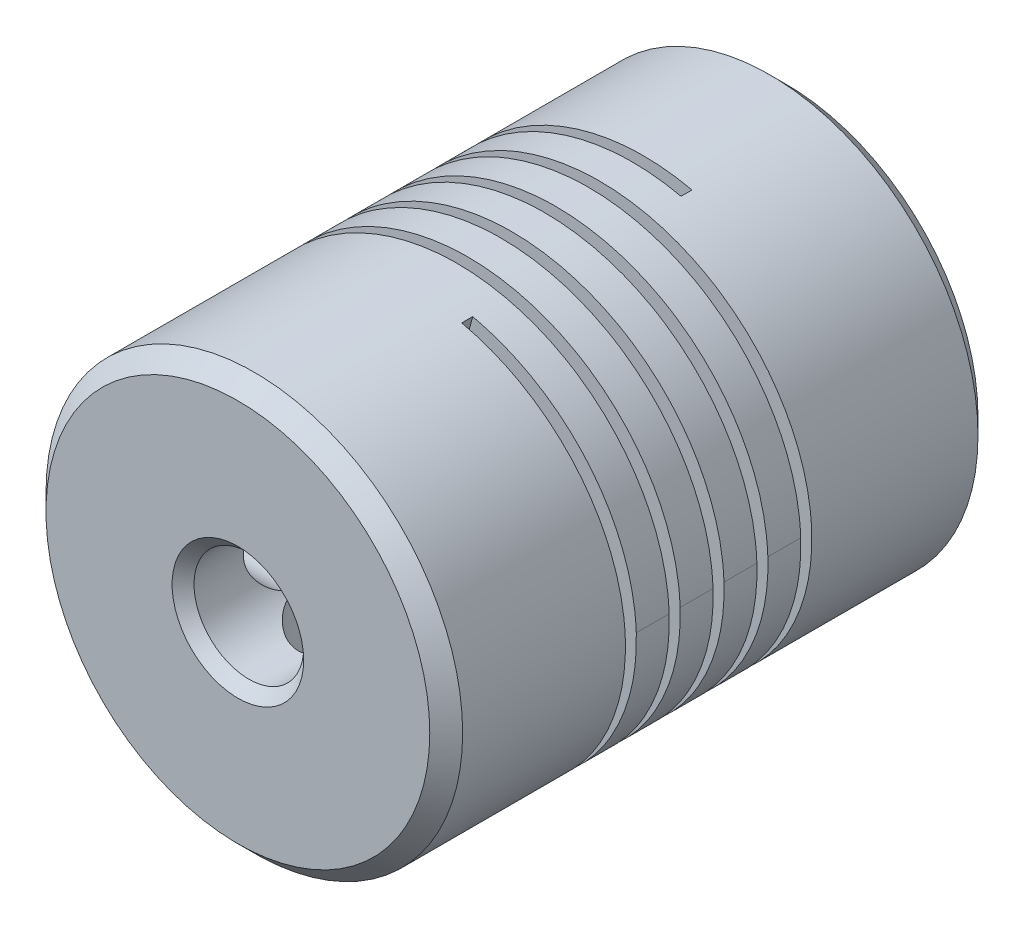
SolidWorks part; units mm, degrees
material "6063-T5"
ref_plane "Спереди" through (0, 0, 0) normal (0, 0, 1) x (1, 0, 0)
ref_plane "Сверху" through (0, 0, 0) normal (0, 1, 0) x (1, 0, 0)
ref_plane "Справа" through (0, 0, 0) normal (1, 0, 0) x (0, 0, -1)
sketch "Эскиз1" plane through (0, 0, 0) normal (0, 0, 1) x (1, 0, 0)
  circle A0 centre (0, 0) radius 9.5
  dimension "D1" = 19
extrude "Body" add sketch "Эскиз1" along normal blind 25
sketch "Эскиз2" plane through (0, 0, 25) normal (0, 0, 1) x (1, 0, 0)
  circle A0 centre (0, 0) radius 2.5
  dimension "D1" = 5
extrude "RodHole" cut sketch "Эскиз2" against normal blind 42
chamfer "OuterChamfer" distance 0.75 angle 45 2 edges at (9.5, 0, 25) (9.5, 0, 0)
chamfer "InnerChamfer" distance 0.5 angle 45 2 edges at (2.5, 0, 25) (2.5, 0, 0)
sketch "Эскиз3" plane through (0, 0, 0) normal (1, 0, 0) x (0, 0, -1)
  circle A0 centre (-4.5, 0) radius 1.75
  circle A1 centre (-20.5, 0) radius 1.75
  dimension "D1" = 3.5
  dimension "D2" = 3.5
  dimension "D3" = 4.5
  dimension "D4" = 20.5
extrude "SetScrewHoles1" cut sketch "Эскиз3" against normal blind 12
cosmetic thread "Условное изображение резьбы1" parameters "D2"=4
cosmetic thread "Условное изображение резьбы2" parameters "D2"=4
sketch "Эскиз4" plane through (0, 0, 0) normal (0, 1, 0) x (1, 0, 0)
  circle A0 centre (0, -4.5) radius 1.75
  circle A1 centre (0, -20.5) radius 1.75
  dimension "D1" = 3.5
  dimension "D2" = 3.5
  dimension "D3" = 4.5
  dimension "D4" = 20.5
extrude "SetScrewHoles2" cut sketch "Эскиз4" against normal blind 12
cosmetic thread "Условное изображение резьбы3" parameters "D2"=4
cosmetic thread "Условное изображение резьбы4" parameters "D2"=4
ref_plane "ReferencePlane1" through (0, 0, 17) normal (0, 0, 1) x (1, 0, 0)
sketch "Эскиз6" plane through (0, 0, 17) normal (0, 0, 1) x (1, 0, 0)
  circle A0 centre (0, 0) radius 9.5
curve "SlotTrajectory" pitch 2 height 10 radius 9.5 centre (0, 0, 17) axis (0, 0, -1) start towards (0.2588, 0.9659, 0)
ref_plane "ReferencePlane2" through (0, 0, 0) normal (0.9659, -0.2588, 0) x (0, 0, -1)
sketch "Эскиз7" plane through (0, 0, 0) normal (0.9659, -0.2588, 0) x (0, 0, -1)
  line L0 (-0.75, 9.5) -> (-24.25, 9.5) construction
  line L1 (-6.75, 10.0798) -> (-7.25, 10.0798)
  line L2 (-6.75, 10.0798) -> (-6.75, 1.4319)
  line L3 (-6.75, 1.4319) -> (-7.25, 1.4319)
  line L4 (-7.25, 10.0798) -> (-7.25, 1.4319)
  spline S0 degree 3 poles (-17, 9.5) (-16.9586, 9.5) (-16.8749, 9.0054) (-16.75, 6.8924) (-16.625, 3.7301) (-16.5, 0) (-16.375, -3.7301) (-16.25, -6.8924) (-16.125, -9.0054) (-16, -9.7473) (-15.875, -9.0054) (-15.75, -6.8924) (-15.625, -3.7301) (-15.5, 0) (-15.375, 3.7301) (-15.25, 6.8924) (-15.125, 9.0054) (-15, 9.7473) (-14.875, 9.0054) (-14.75, 6.8924) (-14.625, 3.7301) (-14.5, 0) (-14.375, -3.7301) (-14.25, -6.8924) (-14.125, -9.0054) (-14, -9.7473) (-13.875, -9.0054) (-13.75, -6.8924) (-13.625, -3.7301) (-13.5, 0) (-13.375, 3.7301) (-13.25, 6.8924) (-13.125, 9.0054) (-13, 9.7473) (-12.875, 9.0054) (-12.75, 6.8924) (-12.625, 3.7301) (-12.5, 0) (-12.375, -3.7301) (-12.25, -6.8924) (-12.125, -9.0054) (-12, -9.7473) (-11.875, -9.0054) (-11.75, -6.8924) (-11.625, -3.7301) (-11.5, 0) (-11.375, 3.7301) (-11.25, 6.8924) (-11.125, 9.0054) (-11, 9.7473) (-10.875, 9.0054) (-10.75, 6.8924) (-10.625, 3.7301) (-10.5, 0) (-10.375, -3.7301) (-10.25, -6.8924) (-10.125, -9.0054) (-10, -9.7473) (-9.875, -9.0054) (-9.75, -6.8924) (-9.625, -3.7301) (-9.5, 0) (-9.375, 3.7301) (-9.25, 6.8924) (-9.125, 9.0054) (-9, 9.7473) (-8.875, 9.0054) (-8.75, 6.8924) (-8.625, 3.7301) (-8.5, 0) (-8.375, -3.7301) (-8.25, -6.8924) (-8.125, -9.0054) (-8, -9.7473) (-7.875, -9.0054) (-7.75, -6.8924) (-7.625, -3.7301) (-7.5, 0) (-7.375, 3.7301) (-7.25, 6.8924) (-7.1251, 9.0054) (-7.0414, 9.5) (-7, 9.5) knots 0 0 0 0 0.0125 0.025 0.0375 0.05 0.0625 0.075 0.0875 0.1 0.1125 0.125 0.1375 0.15 0.1625 0.175 0.1875 0.2 0.2125 0.225 0.2375 0.25 0.2625 0.275 0.2875 0.3 0.3125 0.325 0.3375 0.35 0.3625 0.375 0.3875 0.4 0.4125 0.425 0.4375 0.45 0.4625 0.475 0.4875 0.5 0.5125 0.525 0.5375 0.55 0.5625 0.575 0.5875 0.6 0.6125 0.625 0.6375 0.65 0.6625 0.675 0.6875 0.7 0.7125 0.725 0.7375 0.75 0.7625 0.775 0.7875 0.8 0.8125 0.825 0.8375 0.85 0.8625 0.875 0.8875 0.9 0.9125 0.925 0.9375 0.95 0.9625 0.975 0.9875 1 1 1 1 construction
  point P0 (-7, 9.5)
  dimension "D1" = 0.5
  dimension "D2" = 0.25
sweep "Slot" cut profiles "Эскиз7" path "SlotTrajectory" align with end faces yes
